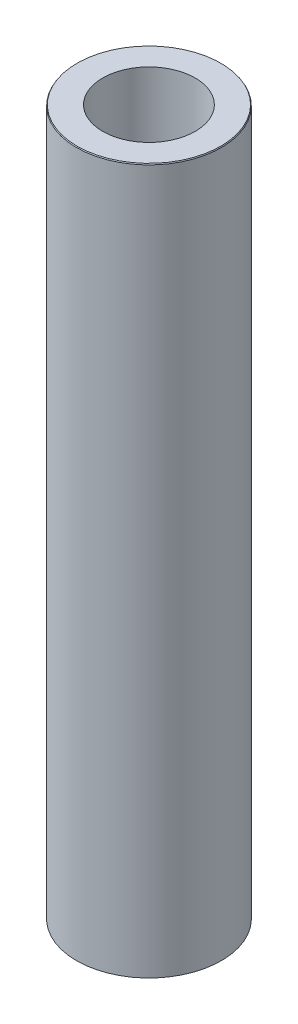
SolidWorks part; units mm, degrees
ref_plane "Front Plane" through (0, 0, 0) normal (0, 0, 1) x (1, 0, 0)
ref_plane "Top Plane" through (0, 0, 0) normal (0, 1, 0) x (1, 0, 0)
ref_plane "Right Plane" through (0, 0, 0) normal (1, 0, 0) x (0, 0, -1)
sketch "Sketch1" plane through (0, 0, 0) normal (0, 1, 0) x (1, 0, 0)
  circle A0 centre (0, 0) radius 57.5
  dimension "SHAFT_OD" = 115
extrude "Boss-Extrude1" add sketch "Sketch1" along normal blind 560.3207
sketch "Sketch2" plane through (0, 0, 0) normal (0, 1, 0) x (1, 0, 0)
  circle A0 centre (0, 0) radius 36.747
  dimension "BORE_D" = 73.494
extrude "Cut-Extrude1" cut sketch "Sketch2" along normal through all
chamfer "Chamfer1" distance 0.7574 angle 30 2 edges at (0, 560.3207, 57.5) (0, 0, 57.5) first distance on face at (0, 560.3207, 57.5) first distance on face at (0, 0, 36.747)
